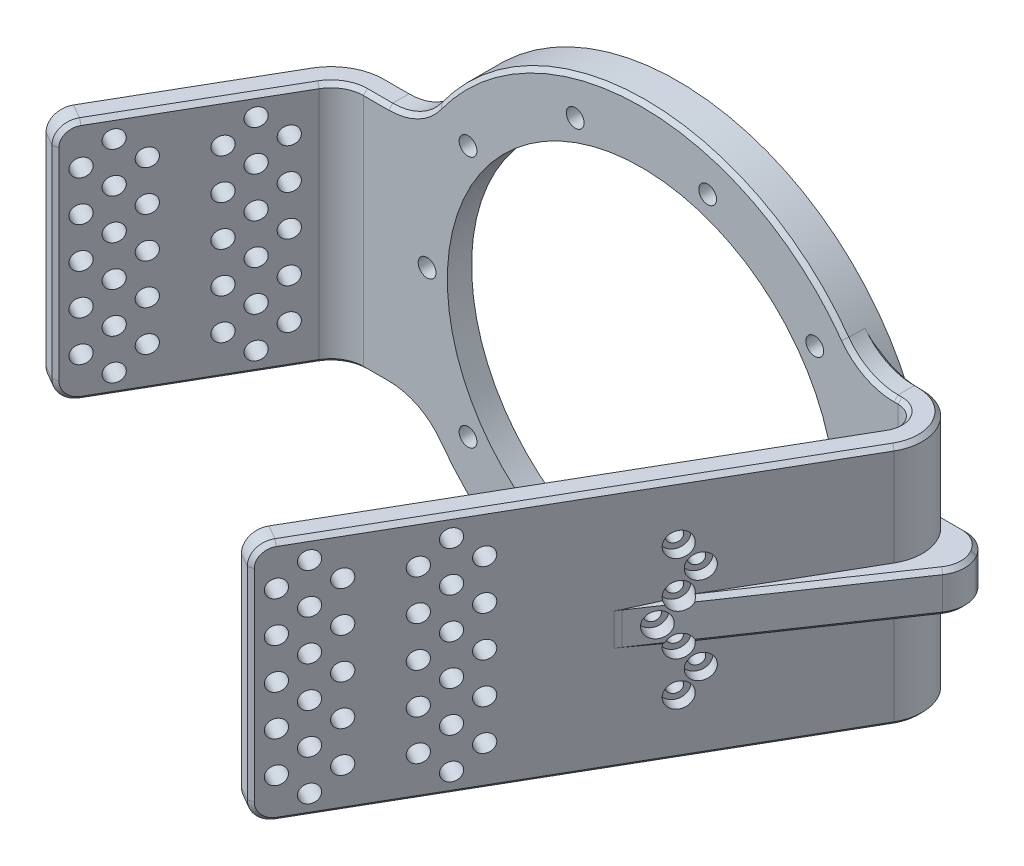
SolidWorks part; units mm, degrees
material "7075-T6 (SN)"
ref_plane "前视基准面" through (0, 0, 0) normal (0, 0, 1) x (1, 0, 0)
ref_plane "上视基准面" through (0, 0, 0) normal (0, 1, 0) x (1, 0, 0)
ref_plane "右视基准面" through (0, 0, 0) normal (1, 0, 0) x (0, 0, -1)
sketch "草图1" plane through (0, 0, 0) normal (0, 0, 1) x (1, 0, 0)
  line L1 (62, 30) -> (62, -30)
  line L2 (-62, 30) -> (-62, -30)
  line L3 (62, 30) -> (54.2586, 30)
  line L4 (62, -30) -> (54.2586, -30)
  line L5 (-54.2586, 30) -> (-62, 30)
  line L7 (-54.2586, -30) -> (-62, -30)
  arc A0 (43.6921, 30) -> (43.6921, -30) centre (0, 0) ccw construction
  arc A1 (51.9615, 30) -> (-51.9615, 30) centre (0, 0) ccw construction
  circle A2 centre (0, 0) radius 48
  arc A3 (54.2586, 30) -> (-54.2586, 30) centre (0, 0) ccw
  circle A4 centre (0, 0) radius 53 construction
  circle A5 centre (0, 0) radius 60 construction
  circle A6 centre (0, 0) radius 62 construction
  arc A8 (-54.2586, -30) -> (54.2586, -30) centre (0, 0) ccw
  point P12 (62, 0)
  point P15 (-62, 0)
  dimension "D1" = 5
  dimension "D2" = 2
extrude "凸台-拉伸1" add sketch "草图1" along normal blind 6
sketch "草图2" plane through (0, -30, 0) normal (0, -1, 0) x (1, 0, 0)
  line L0 (-99.738, 51.6754) -> (-73.3673, 6)
  line L1 (-104.9342, 48.6754) -> (-76.8314, 0)
  line L2 (-62, 0) -> (-54.2586, 0) construction
  line L3 (-62, 6) -> (-54.2586, 6) construction
  line L4 (-76.8314, 0) -> (-62, 0)
  line L5 (-73.3673, 6) -> (-62, 6)
  line L6 (9.3812, 114.6754) -> (72.125, 6)
  line L7 (14.5773, 117.6754) -> (82.5173, 0)
  line L8 (-104.9342, 48.6754) -> (-81.0842, 7.366) construction
  line L9 (-99.738, 51.6754) -> (-75.888, 10.366) construction
  line L10 (9.3812, 114.6754) -> (33.2312, 73.366) construction
  line L11 (14.5773, 117.6754) -> (38.4273, 76.366) construction
  line L12 (-104.9342, 48.6754) -> (-99.738, 51.6754)
  line L13 (9.3812, 114.6754) -> (14.5773, 117.6754)
  line L14 (-62, 0) -> (-62, 6)
  line L15 (62, 6) -> (62, 0)
  line L16 (62, 6) -> (72.125, 6)
  line L17 (62, 0) -> (82.5173, 0)
  dimension "D1" = 6
  dimension "D2" = 6
extrude "凸台-拉伸2" add sketch "草图2" against normal up to surface (60 mm away) up to face at (-58.1293, 30, 3)
fillet "圆角3" radius 8 1 edges at (-73.3673, 0, 6)
fillet "圆角4" radius 14 1 edges at (-76.8314, 0, 0)
fillet "圆角6" radius 5 4 edges at (11.9793, -30, 116.1754) (11.9793, 30, 116.1754) (-102.3361, 30, 50.1754) (-102.3361, -30, 50.1754)
fillet "圆角7" radius 5 1 edges at (72.125, 0, 6)
fillet "圆角8" radius 11 1 edges at (82.5173, 0, 0)
fillet "圆角9" radius 15 4 edges at (-54.2586, -30, 3) (-54.2586, 30, 3) (54.2586, 30, 3) (54.2586, -30, 3)
sketch "草图3" plane through (61.888, 0, 35.731) normal (0.866, 0, 0.5) x (0.5, 0, -0.866)
  line L1 (-51.9212, 20) -> (-51.9212, -20) construction
  circle A0 centre (-89.6212, 0) radius 2.2
  circle A1 centre (-89.6212, 10) radius 2.2
  circle A2 centre (-89.6212, 20) radius 2.2
  circle A3 centre (-89.6212, -10) radius 2.2
  circle A4 centre (-89.6212, -20) radius 2.2
  circle A5 centre (-83.6212, 5) radius 2.2
  circle A6 centre (-83.6212, 15) radius 2.2
  circle A7 centre (-83.6212, 25) radius 2.2
  circle A8 centre (-83.6212, -5) radius 2.2
  circle A9 centre (-83.6212, -15) radius 2.2
  circle A10 centre (-83.6212, -25) radius 2.2
  circle A11 centre (-77.6212, -20) radius 2.2
  circle A12 centre (-77.6212, -10) radius 2.2
  circle A13 centre (-77.6212, 0) radius 2.2
  circle A14 centre (-77.6212, 10) radius 2.2
  circle A15 centre (-77.6212, 20) radius 2.2
  circle A16 centre (-63.9212, 0) radius 2.2
  circle A17 centre (-63.9212, 10) radius 2.2
  circle A18 centre (-63.9212, 20) radius 2.2
  circle A19 centre (-63.9212, -10) radius 2.2
  circle A20 centre (-63.9212, -20) radius 2.2
  circle A21 centre (-57.9212, -25) radius 2.2
  circle A22 centre (-57.9212, -15) radius 2.2
  circle A24 centre (-57.9212, -5) radius 2.2
  circle A25 centre (-57.9212, 5) radius 2.2
  circle A26 centre (-57.9212, 15) radius 2.2
  circle A27 centre (-57.9212, 25) radius 2.2
  circle A28 centre (-51.9212, 20) radius 2.2
  circle A29 centre (-51.9212, 10) radius 2.2
  circle A30 centre (-51.9212, 0) radius 2.2
  circle A31 centre (-51.9212, -10) radius 2.2
  circle A32 centre (-51.9212, -20) radius 2.2
extrude "切除-拉伸1" cut sketch "草图3" against normal through all both and the other way through all
sketch "草图6" plane through (0, 0, 0) normal (0, 0, -1) x (-1, 0, 0)
  circle A0 centre (0, 0) radius 60
  circle A1 centre (0, 0) radius 62
extrude "凸台-拉伸3" add sketch "草图6" along normal blind 3
chamfer "倒角3" distance 1 angle 45 1 edges at (-60, 0, -3)
sketch "草图7" plane through (0, 0, -3) normal (0, 0, -1) x (-1, 0, 0)
  circle A0 centre (0, 0) radius 53 construction
  circle A1 centre (-53, 0) radius 2.2
  circle A2 centre (-42.8779, 31.1526) radius 2.2
  circle A3 centre (-16.3779, 50.406) radius 2.2
  circle A4 centre (16.3779, 50.406) radius 2.2
  circle A5 centre (42.8779, 31.1526) radius 2.2
  circle A6 centre (53, 0) radius 2.2
  circle A7 centre (42.8779, -31.1526) radius 2.2
  circle A8 centre (16.3779, -50.406) radius 2.2
  circle A9 centre (-16.3779, -50.406) radius 2.2
  circle A10 centre (-42.8779, -31.1526) radius 2.2
  point P26 (0, 0)
  dimension "D1" = 10
extrude "切除-拉伸3" cut sketch "草图7" against normal blind 11
chamfer "倒角4" distance 1 angle 45 46 edges at (-55.6444, -31.6491, 0) (-65.6152, -30, 0) (-75.7485, -30, 1.8756) (-91.6535, -30, 25.6727) (-104.2019, -28.5355, 47.4072) (-104.9342, 0, 48.6754) (-104.2019, 28.5355, 47.4072) (-91.6535, 30, 25.6727) (-55.6444, 31.6491, 0) (-75.7485, 30, 1.8756) (-65.6152, 30, 0) (-72.7485, -30, 7.0718) (-86.4573, -30, 28.6727) (-65.6152, -30, 6) (-99.0058, -28.5355, 50.4072) (-55.6444, -31.6491, 6) (-99.738, 0, 51.6754) (0, -62, 6) (-99.0058, 28.5355, 50.4072) (55.6444, -31.6491, 6) (-86.4573, 30, 28.6727) (62.9734, -30, 6) (-72.7485, 30, 7.0718) (67.7949, -30, 8.5) (-65.6152, 30, 6) (39.838, -30, 61.9227) (-55.6444, 31.6491, 6) (10.1134, -28.5355, 113.4072) (0, 62, 6) (9.3812, 0, 114.6754) (55.6444, 31.6491, 6) (10.1134, 28.5355, 113.4072) (62.9734, 30, 6) (39.838, 30, 61.9227) (67.7949, 30, 8.5) (45.0342, -30, 64.9227) (55.6444, -31.6491, 0) (62.9734, -30, 0) (72.991, -30, 5.5) (15.3096, -28.5355, 116.4072) (14.5773, 0, 117.6754) (15.3096, 28.5355, 116.4072) (55.6444, 31.6491, 0) (45.0342, 30, 64.9227) (62.9734, 30, 0) (72.991, 30, 5.5)
sketch "草图8" plane through (0, 0, 0) normal (0, 1, 0) x (1, 0, 0)
  line L0 (63.4647, 0) -> (78.4647, 0)
  line L2 (72.991, -16.5) -> (47.991, -59.8013)
  line L4 (78.4647, 0) -> (83.1358, -8.0905)
  line L5 (72.991, -16.5) -> (17.0773, -113.3453) construction
  line L7 (47.991, -59.8013) -> (83.1358, -8.0905)
  arc A0 (72.991, -16.5) -> (63.4647, 0) centre (63.4647, -11) ccw construction
  arc A1 (72.991, -16.5) -> (63.4647, 0) centre (63.4647, -11) ccw
extrude "凸台-拉伸5" add sketch "草图8" along normal mid plane 10
fillet "圆角17" radius 20 1 edges at (47.991, 0, 59.8013)
fillet "圆角19" radius 7.5 2 edges at (83.1358, 0, 8.0905) (78.4647, 0, 0)
chamfer "倒角7" distance 1 angle 45 12 edges at (48.0024, -5, 59.8084) (64.4473, -5, 35.5881) (81.7831, -5, 8.0408) (80.7066, -5, 3.883) (77.8846, -5, 1.0048) (68.7997, -5, 0) (48.0024, 5, 59.8084) (64.4473, 5, 35.5881) (81.7831, 5, 8.0408) (80.7066, 5, 3.883) (77.8846, 5, 1.0048) (68.7997, 5, 0)
sketch "草图21" plane through (61.888, 0, 35.731) normal (0.866, 0, 0.5) x (0.5, 0, -0.866)
  line L0 (-77.6212, 0) -> (-16.79, 0) construction
  line L1 (-16.79, 0) -> (-16.79, -5.375)
  line L4 (-16.79, -5.375) -> (-16.79, -10.75)
  line L5 (-16.79, -10.75) -> (-16.79, -16.125)
  line L6 (-16.79, 0) -> (-20.79, 0)
  line L7 (-16.79, 0) -> (-16.79, 5.375)
  line L8 (-16.79, 5.375) -> (-16.79, 10.75)
  line L9 (-16.79, 10.75) -> (-16.79, 16.125)
  line L10 (-16.79, 10.75) -> (-12.79, 10.75)
  line L11 (-16.79, -10.75) -> (-12.79, -10.75)
  point P9 (-16.79, -10.75)
hole_wizard "打孔尺寸(%根据)内六角圆柱头螺钉的类型0" positions "草图22" profile "草图23" counterbore size "M3" standard "GB"
sketch "草图22" plane through (61.888, 0, 35.731) normal (0.866, 0, 0.5) x (0.5, 0, -0.866)
  point P0 (-16.79, 16.125)
  point P3 (-12.79, 10.75)
  point P6 (-16.79, 5.375)
  point P9 (-20.79, 0)
  point P12 (-16.79, -5.375)
  point P15 (-12.79, -10.75)
  point P18 (-16.79, -16.125)
sketch "草图23" plane through (53.493, 16.125, 50.2716) normal (0, 1, 0) x (0.5, 0, -0.866)
  line L0 (0, 0) -> (0, 8.5215)
  line L1 (0, 8.5215) -> (1.7, 7.5)
  line L2 (1.7, 7.5) -> (1.7, 3)
  line L3 (1.7, 3) -> (3, 3)
  line L4 (3, 3) -> (3, 0)
  line L5 (3, 0) -> (0, 0)
  line L10 (0, 8.5215) -> (-1.7, 7.5) construction
  line L11 (0, -6.35) -> (0, 107.95) construction
  dimension "孔直径" = 3.4
  dimension "孔深度" = 7.5
  dimension "柱形沉头孔直径" = 6
  dimension "柱形沉头孔深度" = 3
  dimension "导头角度" = 118
sketch "草图24" plane through (59.2899, 0, 34.231) normal (0.866, 0, 0.5) x (0.5, 0, -0.866)
  circle A0 centre (-16.79, -5.375) radius 3 construction
  circle A1 centre (-16.79, 5.375) radius 3 construction
  circle A2 centre (-16.79, -5.375) radius 3
  circle A3 centre (-16.79, 5.375) radius 3
  circle A5 centre (-20.79, 0) radius 3
  circle A6 centre (-20.79, 0) radius 3
  dimension "D1" = 0
extrude "切除-拉伸4" cut sketch "草图24" along normal blind 8
